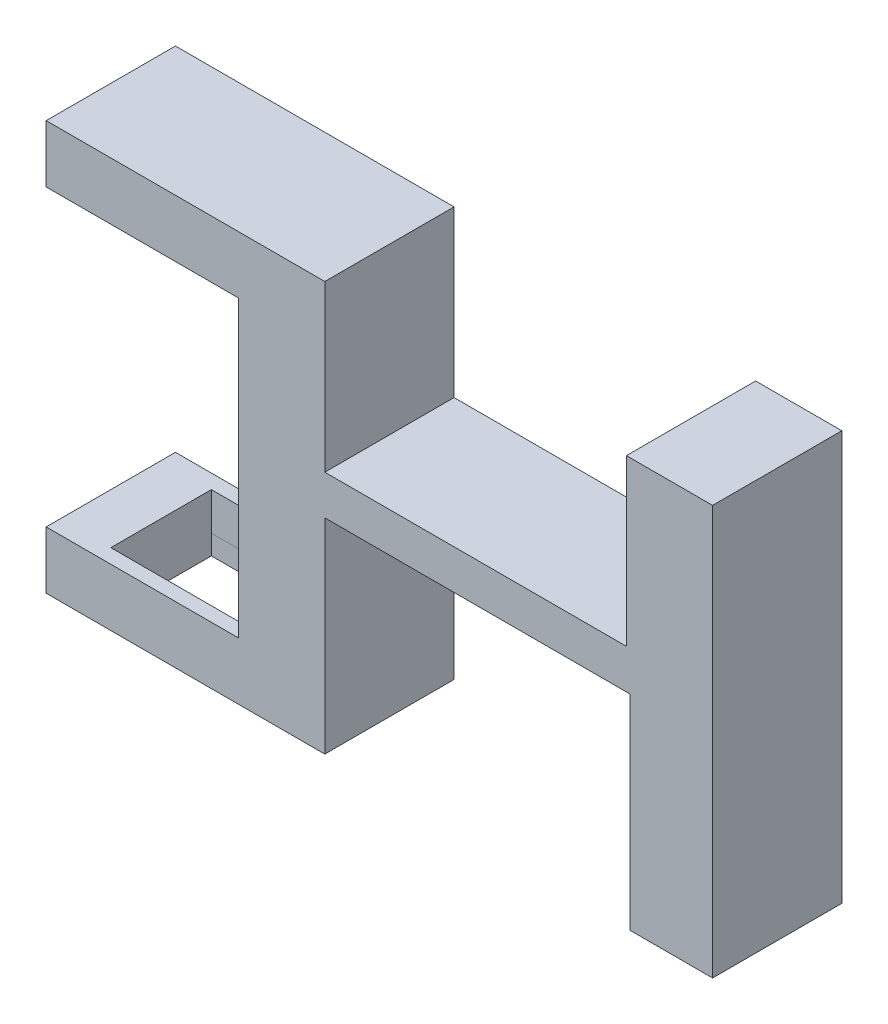
SolidWorks part; units mm, degrees
ref_plane "Front Plane" through (0, 0, 0) normal (0, 0, 1) x (1, 0, 0)
ref_plane "Top Plane" through (0, 0, 0) normal (0, 1, 0) x (1, 0, 0)
ref_plane "Right Plane" through (0, 0, 0) normal (1, 0, 0) x (0, 0, -1)
sketch "Sketch2" plane through (0, 0, 0) normal (0, 0, 1) x (1, 0, 0)
  line L0 (0, -55) -> (0, 55) construction
  line L1 (0, 55) -> (66, 55)
  line L2 (0, 55) -> (0, 0)
  line L3 (0, 0) -> (66, 0)
  line L4 (66, 55) -> (66, 0)
  line L5 (55, 0) -> (-55, 0) construction
  line L7 (12, 50.75) -> (54, 50.75)
  line L8 (12, 50.75) -> (12, 30.25)
  line L9 (12, 30.25) -> (54, 30.25)
  line L10 (54, 50.75) -> (54, 30.25)
  line L11 (12, 24.75) -> (54.5, 24.75)
  line L12 (12, 24.75) -> (12, 4.25)
  line L13 (12, 4.25) -> (54.5, 4.25)
  line L14 (54.5, 24.75) -> (54.5, 4.25)
  dimension "D1" = 55
  dimension "D2" = 12
  dimension "D3" = 42
  dimension "D4" = 20.5
  dimension "D5" = 5.5
  dimension "D6" = 42.5
  dimension "D7" = 20.5
  dimension "D8" = 12
  dimension "D9" = 4.25
  dimension "D10" = 12
extrude "Boss-Extrude1" add sketch "Sketch2" along normal blind 18
sketch "Sketch3" plane through (0, 0, 18) normal (0, 0, 1) x (1, 0, 0)
  line L2 (12, 24.75) -> (12, 4.25) construction
  line L3 (54.5, 24.75) -> (12, 24.75) construction
  circle A8 centre (8.15, 19.75) radius 2.5
  circle A9 centre (8.15, 9.75) radius 2.5
  circle A10 centre (57.85, 9.75) radius 2.5
  circle A11 centre (57.85, 19.75) radius 2.5
  dimension "D9" = 45.85
  dimension "D10" = 45.85
  dimension "D11" = 5
  dimension "D12" = 5
  dimension "D13" = 3.85
  dimension "D14" = 3.85
  dimension "D15" = 10
  dimension "D16" = 5
  dimension "D17" = 5
  dimension "D18" = 5
  dimension "D19" = 5
  dimension "D24" = 10
sketch "Sketch5" plane through (0, 0, 0) normal (-1, 0, 0) x (0, 0, 1)
  line L0 (0, -31.35) -> (0, 31.35) construction
  line L1 (0, 55) -> (2, 55)
  line L2 (0, 55) -> (0, 49)
  line L3 (0, 49) -> (2, 49)
  line L4 (2, 55) -> (2, 49)
  line L5 (18, 55) -> (0, 55) construction
  line L6 (9.9, 0) -> (-9.9, 0) construction
  line L7 (18, 55) -> (16, 55)
  line L8 (18, 55) -> (18, 49)
  line L9 (18, 49) -> (16, 49)
  line L10 (16, 55) -> (16, 49)
  line L11 (0, 0) -> (2, 0)
  line L12 (0, 0) -> (0, 6)
  line L13 (0, 6) -> (2, 6)
  line L14 (2, 0) -> (2, 6)
  line L15 (18, 0) -> (16, 0)
  line L16 (18, 0) -> (18, 6)
  line L17 (18, 6) -> (16, 6)
  line L18 (16, 0) -> (16, 6)
  line L19 (18, 55) -> (18, 0) construction
  dimension "D1" = 2
  dimension "D2" = 2
  dimension "D3" = 6
  dimension "D4" = 6
  dimension "D5" = 2
  dimension "D6" = 2
  dimension "D7" = 6
  dimension "D8" = 6
extrude "Boss-Extrude2" add sketch "Sketch5" along normal blind 26.8
sketch "Sketch6" plane through (0, 0, 2) normal (0, 0, 1) x (1, 0, 0)
  line L0 (-26.8, 49) -> (0, 49) construction
  line L1 (-23.8, 49) -> (-26.8, 49)
  line L2 (-23.8, 49) -> (-23.8, 55)
  line L3 (-23.8, 55) -> (-26.8, 55)
  line L4 (-26.8, 49) -> (-26.8, 55)
  line L5 (66, 55) -> (-26.8, 55) construction
  line L6 (-26.8, 55) -> (-26.8, 49) construction
  line L7 (9.9, 0) -> (-9.9, 0) construction
  line L8 (-26.8, 6) -> (-24.8, 6)
  line L9 (-26.8, 6) -> (-26.8, 0)
  line L10 (-26.8, 0) -> (-24.8, 0)
  line L11 (-24.8, 6) -> (-24.8, 0)
  dimension "D1" = 3
  dimension "D2" = 2
extrude "Boss-Extrude3" add sketch "Sketch6" along normal up to next
sketch "Sketch8" plane through (0, 0, 18) normal (0, 0, 1) x (1, 0, 0)
  line L0 (66, 55) -> (-26.8, 55) construction
  line L1 (12, 50.75) -> (54, 50.75)
  line L2 (12, 50.75) -> (12, 55)
  line L3 (12, 55) -> (54, 55)
  line L4 (54, 50.75) -> (54, 55)
  line L5 (9.9, 0) -> (-9.9, 0) construction
  line L6 (12, 4.25) -> (54.5, 4.25)
  line L7 (12, 4.25) -> (12, 0)
  line L8 (12, 0) -> (54.5, 0)
  line L9 (54.5, 4.25) -> (54.5, 0)
extrude "Cut-Extrude3" cut sketch "Sketch8" against normal up to next
sketch "Sketch12" plane through (0, 0, 2) normal (0, 0, 1) x (1, 0, 0)
  line L0 (-26.8, 6) -> (0, 6) construction
  line L1 (-8, 6) -> (-5, 6)
  line L2 (-8, 6) -> (-8, 0)
  line L3 (-8, 0) -> (-5, 0)
  line L4 (-5, 6) -> (-5, 0)
  line L5 (9.9, 0) -> (-9.9, 0) construction
  line L6 (0, -9.9) -> (0, 9.9) construction
  dimension "D1" = 3
  dimension "D2" = 5
extrude "Boss-Extrude7" add sketch "Sketch12" along normal up to surface (14 mm away) up to face at (-12.4, 3, 16)
sketch "Sketch14" plane through (-8, 0, 0) normal (-1, 0, 0) x (0, 0, 1)
  line L0 (18, 6) -> (0, 6) construction
  line L1 (7, 6) -> (11, 6)
  line L2 (7, 6) -> (7, 0)
  line L3 (7, 0) -> (11, 0)
  line L4 (11, 6) -> (11, 0)
  line L5 (9.9, 0) -> (-9.9, 0) construction
  line L6 (0, -30.25) -> (0, 30.25) construction
  line L7 (18, 0) -> (18, 6) construction
  dimension "D1" = 7
  dimension "D2" = 7
extrude "Boss-Extrude8" add sketch "Sketch14" along normal up to surface (16.8 mm away) up to face at (-24.8, 3, 9)
sketch "Sketch17" plane through (0, 0, 2) normal (0, 0, 1) x (1, 0, 0)
  line L1 (-23.8, 55) -> (0, 55)
  line L2 (-23.8, 55) -> (-23.8, 49)
  line L3 (-23.8, 49) -> (0, 49)
  line L4 (0, 55) -> (0, 49)
extrude "Boss-Extrude9" add sketch "Sketch17" along normal blind 14 and the other way blind 1
sketch "Sketch18" plane through (0, 6, 0) normal (0, 1, 0) x (1, 0, 0)
  line L1 (-5, -2) -> (-24.8, -2)
  line L2 (-5, -2) -> (-5, -16)
  line L3 (-5, -16) -> (-24.8, -16)
  line L4 (-24.8, -2) -> (-24.8, -16)
extrude "Cut-Extrude4" cut sketch "Sketch18" against normal blind 10
sketch "Sketch20" plane through (0, 6, 0) normal (0, 1, 0) x (1, 0, 0)
  line L0 (-24.8, -16) -> (0, -16) construction
  line L1 (-24.8, -2) -> (-19.8, -2)
  line L2 (-24.8, -2) -> (-24.8, -16)
  line L3 (-24.8, -16) -> (-19.8, -16)
  line L4 (-19.8, -2) -> (-19.8, -16)
  dimension "D1" = 5
extrude "Boss-Extrude10" add sketch "Sketch20" against normal blind 6
sketch "Sketch22" plane through (0, 55, 0) normal (0, 1, 0) x (1, 0, 0)
  line L0 (-30.25, 0) -> (30.25, 0) construction
  line L1 (-26.8, -18) -> (12, -18)
  line L2 (-26.8, -18) -> (-26.8, 0)
  line L3 (-26.8, 0) -> (12, 0)
  line L4 (12, -18) -> (12, 0)
  line L5 (12, -18) -> (12, 0) construction
extrude "Boss-Extrude11" add sketch "Sketch22" along normal blind 1
sketch "Sketch23" plane through (0, 49, 0) normal (0, -1, 0) x (1, 0, 0)
  line L1 (0, 18) -> (-26.8, 18)
  line L2 (0, 18) -> (0, 0)
  line L3 (0, 0) -> (-26.8, 0)
  line L4 (-26.8, 18) -> (-26.8, 0)
extrude "Boss-Extrude12" add sketch "Sketch23" along normal blind 1
sketch "Sketch24" plane through (0, 6, 0) normal (0, 1, 0) x (1, 0, 0)
  line L0 (0, 0) -> (-26.8, 0)
  line L1 (-26.8, 0) -> (-26.8, -18)
  line L2 (-26.8, -18) -> (0, -18)
  line L3 (0, -18) -> (0, -16)
  line L4 (0, -16) -> (-19.8, -16)
  line L5 (-19.8, -16) -> (-19.8, -2)
  line L6 (-19.8, -2) -> (0, -2)
  line L7 (0, -2) -> (0, 0)
extrude "Boss-Extrude13" add sketch "Sketch24" along normal blind 1
sketch "Sketch25" plane through (0, 55, 0) normal (0, 1, 0) x (1, 0, 0)
  line L0 (-30.25, 0) -> (30.25, 0) construction
  line L1 (66, -18) -> (54, -18)
  line L2 (66, -18) -> (66, 0)
  line L3 (66, 0) -> (54, 0)
  line L4 (54, -18) -> (54, 0)
  line L5 (54, -18) -> (54, 0) construction
extrude "Boss-Extrude14" add sketch "Sketch25" along normal blind 1
sketch "Sketch27" plane through (0, 0, 0) normal (0, -1, 0) x (1, 0, 0)
  line L0 (-26.8, 18) -> (12, 18)
  line L1 (12, 18) -> (12, 0)
  line L2 (30.25, 0) -> (-30.25, 0) construction
  line L3 (12, 18) -> (12, 0) construction
  line L4 (12, 0) -> (-26.8, 0)
  line L5 (-26.8, 0) -> (-26.8, 18) construction
  line L6 (-26.8, 0) -> (-26.8, 18)
  line L7 (-19.8, 16) -> (-19.8, 2)
  line L8 (-19.8, 2) -> (0, 2)
  line L9 (0, 2) -> (0, 16)
  line L10 (0, 16) -> (0, 2) construction
  line L11 (-19.8, 16) -> (0, 16) construction
  line L12 (0, 16) -> (-19.8, 16)
extrude "Boss-Extrude15" add sketch "Sketch27" along normal blind 1
sketch "Sketch28" plane through (0, 0, 0) normal (0, -1, 0) x (1, 0, 0)
  line L0 (30.25, 0) -> (-30.25, 0) construction
  line L1 (54.5, 18) -> (66, 18)
  line L2 (54.5, 18) -> (54.5, 0)
  line L3 (54.5, 0) -> (66, 0)
  line L4 (66, 18) -> (66, 0)
  line L5 (66, 18) -> (66, 0) construction
extrude "Boss-Extrude16" add sketch "Sketch28" along normal blind 1
sketch "Sketch32" plane through (-26.8, 0, 0) normal (-1, 0, 0) x (0, 0, 1)
  line L0 (0, -30.25) -> (0, 30.25) construction
  line L1 (18, 7) -> (0, 7)
  line L2 (18, 7) -> (18, 4.25)
  line L3 (18, 4.25) -> (0, 4.25)
  line L4 (0, 7) -> (0, 4.25)
  dimension "D1" = 2.75
extrude "Cut-Extrude8" cut sketch "Sketch32" against normal blind 26.8
sketch "Sketch33" plane through (0, -1, 0) normal (0, -1, 0) x (1, 0, 0)
  line L0 (-26.8, 18) -> (12, 18)
  line L1 (12, 18) -> (12, 0)
  line L2 (30.25, 0) -> (-30.25, 0) construction
  line L3 (12, 18) -> (12, 0) construction
  line L4 (12, 0) -> (-26.8, 0)
  line L5 (-26.8, 18) -> (-26.8, 0) construction
  line L6 (-26.8, 0) -> (-26.8, 18)
  line L7 (-19.8, 16) -> (0, 16)
  line L8 (0, -9.9) -> (0, 9.9) construction
  line L9 (0, 16) -> (-19.8, 16) construction
  line L10 (0, 16) -> (0, 1.9658)
  line L11 (0, 1.9658) -> (-19.8, 2)
  line L12 (-19.8, 2) -> (-19.8, 16)
extrude "Boss-Extrude17" add sketch "Sketch33" along normal blind 2.75
sketch "Sketch34" plane through (0, -1, 0) normal (0, -1, 0) x (1, 0, 0)
  line L0 (30.25, 0) -> (-30.25, 0) construction
  line L1 (54.5, 18) -> (66, 18)
  line L2 (54.5, 18) -> (54.5, 0)
  line L3 (54.5, 0) -> (66, 0)
  line L4 (66, 18) -> (66, 0)
  line L5 (66, 0) -> (66, 18) construction
extrude "Boss-Extrude18" add sketch "Sketch34" along normal blind 2.75
sketch "Sketch35" plane through (0, 48, 0) normal (0, -1, 0) x (1, 0, 0)
  line L1 (-26.8, 18) -> (0, 18)
  line L2 (-26.8, 18) -> (-26.8, 0)
  line L3 (-26.8, 0) -> (0, 0)
  line L4 (0, 18) -> (0, 0)
extrude "Boss-Extrude19" add sketch "Sketch35" along normal blind 2.75
sketch "Sketch36" plane through (0, 56, 0) normal (0, 1, 0) x (1, 0, 0)
  line L0 (-30.25, 0) -> (30.25, 0) construction
  line L1 (66, -18) -> (54, -18)
  line L2 (66, -18) -> (66, 0)
  line L3 (66, 0) -> (54, 0)
  line L4 (54, -18) -> (54, 0)
  line L5 (54, -18) -> (54, 0) construction
  line L7 (12, -18) -> (-26.8, -18)
  line L8 (12, -18) -> (12, 0)
  line L9 (12, 0) -> (-26.8, 0)
  line L10 (-26.8, -18) -> (-26.8, 0)
extrude "Cut-Extrude9" cut sketch "Sketch36" against normal blind 2.75
sketch "Sketch37" plane through (-26.8, 0, 0) normal (-1, 0, 0) x (0, 0, 1)
  line L0 (0, 53.25) -> (18, 53.25) construction
  line L1 (0, -30.25) -> (0, 30.25) construction
  line L2 (18, 45.25) -> (18, 53.25) construction
  circle A0 centre (4, 49) radius 2.5
  circle A1 centre (14, 49) radius 2.5
  dimension "D1" = 4.25
  dimension "D2" = 4
  dimension "D3" = 4
  dimension "D4" = 4.25
  dimension "D5" = 5
  dimension "D6" = 5
sketch "Sketch38" plane through (-26.8, 0, 0) normal (-1, 0, 0) x (0, 0, 1)
  line L0 (0, 4.25) -> (18, 4.25) construction
  line L1 (0, -30.25) -> (0, 30.25) construction
  line L2 (18, -3.75) -> (18, 4.25) construction
  circle A0 centre (4, 0) radius 2.5
  circle A1 centre (14, 0) radius 2.5
  dimension "D1" = 4.25
  dimension "D2" = 5
  dimension "D3" = 4
  dimension "D4" = 5
  dimension "D5" = 4
  dimension "D6" = 4.25
extrude "Cut-Extrude10" cut sketch "Sketch37" against normal blind 6
extrude "Cut-Extrude11" cut sketch "Sketch38" against normal blind 6
sketch "Sketch39" plane through (0, 0, 0) normal (0, 0, -1) x (-1, 0, 0)
  line L0 (-54, 30.25) -> (-54, 27.5) construction
  line L2 (-54, 27.5) -> (-66, 27.5) construction
  line L3 (-66, -3.75) -> (-66, 53.25) construction
  circle A2 centre (-8.15, 19.75) radius 2.5
  circle A3 centre (-8.15, 9.75) radius 2.5
  circle A6 centre (-57.85, 19.75) radius 2.5
  circle A7 centre (-57.85, 9.75) radius 2.5
  circle A8 centre (-8.15, 45.25) radius 2.5
  circle A9 centre (-8.15, 35.25) radius 2.5
  circle A10 centre (-57.85, 45.25) radius 2.5
  circle A11 centre (-57.85, 35.25) radius 2.5
  dimension "D1" = 2.75
  dimension "D4" = 5
  dimension "D5" = 5
  dimension "D6" = 5
  dimension "D7" = 5
extrude "Cut-Extrude12" cut sketch "Sketch39" against normal blind 10
sketch "Sketch40" plane through (0, 0, 0) normal (0, 0, -1) x (-1, 0, 0)
  line L0 (-57.85, 35.25) -> (-8.15, 35.25) construction
  line L1 (-57.85, 19.75) -> (-8.15, 19.75) construction
